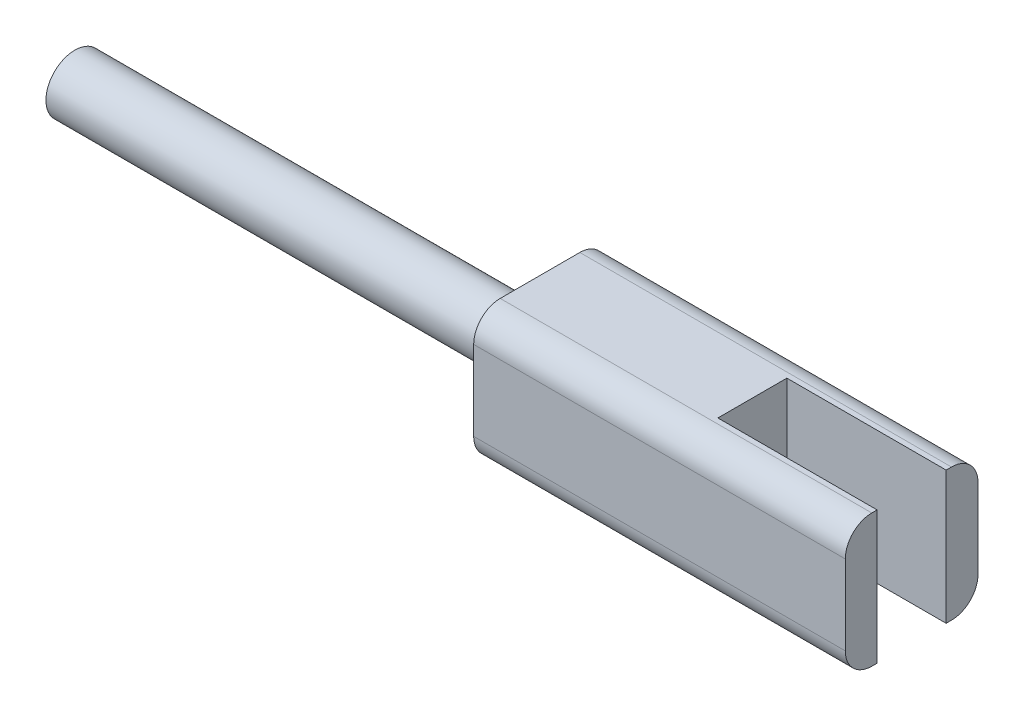
SolidWorks part; units mm, degrees
ref_plane "Front Plane" through (0, 0, 0) normal (0, 0, 1) x (1, 0, 0)
ref_plane "Top Plane" through (0, 0, 0) normal (0, 1, 0) x (1, 0, 0)
ref_plane "Right Plane" through (0, 0, 0) normal (1, 0, 0) x (0, 0, -1)
sketch "Sketch1" plane through (0, 0, 0) normal (1, 0, 0) x (0, 0, -1)
  circle A0 centre (0, 0) radius 1.09
extrude "Boss-Extrude1" add sketch "Sketch1" along normal blind 19.524
ref_plane "Plane1" through (17.524, 0, 0) normal (1, 0, 0) x (0, 0, -1)
sketch "Sketch2" plane through (17.524, 0, 0) normal (1, 0, 0) x (0, 0, -1)
  line L0 (-1.5, -2.5) -> (1.5, -2.5)
  line L1 (2.5, -1.5) -> (2.5, 1.5)
  line L2 (1.5, 2.5) -> (-1.5, 2.5)
  line L3 (-2.5, 1.5) -> (-2.5, -1.5)
  arc A0 (1.5, -2.5) -> (2.5, -1.5) centre (1.5, -1.5) ccw
  arc A1 (2.5, 1.5) -> (1.5, 2.5) centre (1.5, 1.5) ccw
  arc A2 (-1.5, 2.5) -> (-2.5, 1.5) centre (-1.5, 1.5) ccw
  arc A3 (-2.5, -1.5) -> (-1.5, -2.5) centre (-1.5, -1.5) ccw
extrude "Boss-Extrude2" add sketch "Sketch2" along normal blind 14
sketch "Sketch3" plane through (0, 0, 0) normal (0, 1, 0) x (1, 0, 0)
  line L0 (25.524, 1.3) -> (32.524, 1.3)
  line L1 (32.524, 1.3) -> (32.524, -1.3)
  line L2 (32.524, -1.3) -> (25.524, -1.3)
  line L3 (25.524, -1.3) -> (25.524, 1.3)
extrude "Cut-Extrude1" cut sketch "Sketch3" against normal through all and the other way through all
